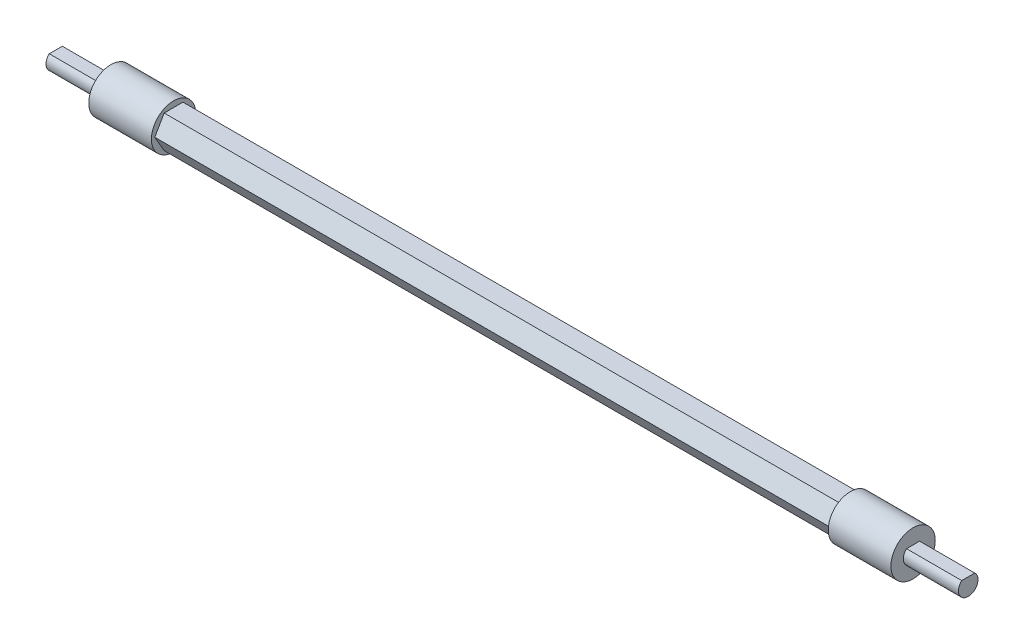
SolidWorks part; units mm, degrees
material "ABS"
ref_plane "Front Plane" through (0, 0, 0) normal (0, 0, 1) x (1, 0, 0)
ref_plane "Top Plane" through (0, 0, 0) normal (0, 1, 0) x (1, 0, 0)
ref_plane "Right Plane" through (0, 0, 0) normal (1, 0, 0) x (0, 0, -1)
sketch "Sketch1" plane through (0, 0, 0) normal (1, 0, 0) x (0, 0, -1)
  line L1 (3.75, 0) -> (1.875, 3.2476)
  line L2 (1.875, 3.2476) -> (-1.875, 3.2476)
  line L3 (-1.875, 3.2476) -> (-3.75, 0)
  line L4 (-3.75, 0) -> (-1.875, -3.2476)
  line L5 (-1.875, -3.2476) -> (1.875, -3.2476)
  line L6 (1.875, -3.2476) -> (3.75, 0)
  circle A0 centre (0, 0) radius 3.75 construction
  circle A1 centre (0, 0) radius 4.425
  dimension "D1" = 8.85
  dimension "D2" = 7.5
extrude "Boss-Extrude1" add sketch "Sketch1" along normal mid plane 135 contours L1 A1 L2 L3 L4 L5 L6 | A1 L3 L4 | A1 L2 L3 | A1 L1 L2 | A1 L6 L1 | A1 L5 L6 | A1 L4 L5 region at (0, 0, 0)
extrude "Boss-Extrude2" add sketch "Sketch1<3>" along normal blind 12.5 from offset 67.5 contours L2 A1 | L1 A1 | L6 A1 | L5 A1 | L4 A1 | L3 A1 | L5 L6 L1 L2 L3 L4 region at (0, 0, 0) region at (0, 0, 4.2998)
sketch "Sketch1<3>" plane through (0, 0, 0) normal (1, 0, 0) x (0, 0, -1) same geometry as "Sketch1"
sketch "Sketch4" plane through (80, 0, 0) normal (1, 0, 0) x (0, 0, -1)
  line L0 (-1.3038, 1.45) -> (1.3038, 1.45)
  circle A1 centre (0, 0) radius 1.95
  circle A2 centre (0, 0) radius 4.425
  circle A3 centre (0, 0) radius 4.425
  dimension "D1" = 3.9
  dimension "D3" = 0.5
  dimension "D2" = 0
extrude "Boss-Extrude4" add sketch "Sketch4" along normal blind 11 contours L0 A1 region at (80, -0.1337, 0)
mirror "Mirror2" about plane through (0, 0, 0) normal (1, 0, 0) of "Boss-Extrude4", "Boss-Extrude2"
